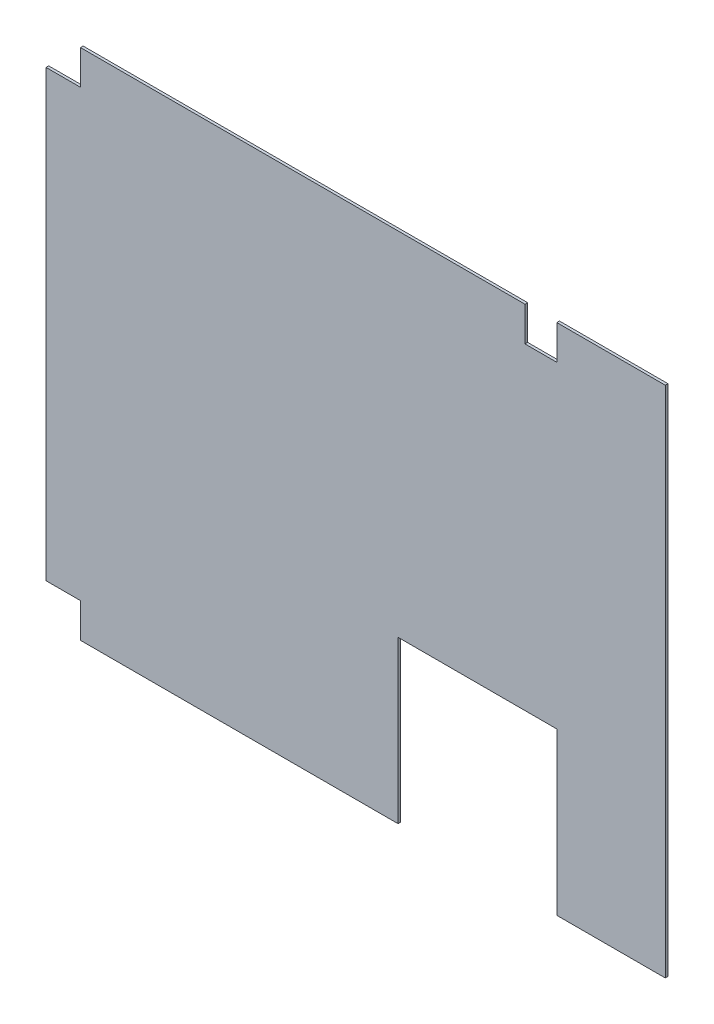
SolidWorks part; units mm, degrees
ref_plane "Front Plane" through (0, 0, 0) normal (0, 0, 1) x (1, 0, 0)
ref_plane "Top Plane" through (0, 0, 0) normal (0, 1, 0) x (1, 0, 0)
ref_plane "Right Plane" through (0, 0, 0) normal (1, 0, 0) x (0, 0, -1)
sketch "Sketch1" plane through (0, 0, 0) normal (0, 0, 1) x (1, 0, 0)
  line L1 (-371.475, -307.975) -> (371.475, -307.975)
  line L2 (-371.475, -307.975) -> (-371.475, 307.975)
  line L3 (-371.475, 307.975) -> (371.475, 307.975)
  line L4 (371.475, -307.975) -> (371.475, 307.975)
  line L5 (-371.475, -307.975) -> (371.475, 307.975) construction
  line L6 (-371.475, 307.975) -> (371.475, -307.975) construction
  point P0 (0, 0)
  dimension "D1" = 742.95
  dimension "D2" = 615.95
extrude "Boss-Extrude1" add sketch "Sketch1" along normal blind 3.175
sketch "Sketch2" plane through (0, 0, 3.175) normal (0, 0, 1) x (1, 0, 0)
  line L0 (371.475, 307.975) -> (-371.475, 307.975) construction
  line L1 (-371.475, 307.975) -> (-330.2, 307.975)
  line L2 (-371.475, 307.975) -> (-371.475, 266.7)
  line L3 (-371.475, 266.7) -> (-330.2, 266.7)
  line L4 (-330.2, 307.975) -> (-330.2, 266.7)
  line L5 (-371.475, 307.975) -> (-371.475, -307.975) construction
  line L6 (371.475, -307.975) -> (371.475, 307.975) construction
  line L7 (-371.475, -307.975) -> (-330.2, -307.975)
  line L8 (-371.475, -307.975) -> (-371.475, -266.7)
  line L9 (-371.475, -266.7) -> (-330.2, -266.7)
  line L10 (-330.2, -307.975) -> (-330.2, -266.7)
  line L11 (203.2, 307.975) -> (241.3, 307.975)
  line L12 (203.2, 307.975) -> (203.2, 266.7)
  line L13 (203.2, 266.7) -> (241.3, 266.7)
  line L14 (241.3, 307.975) -> (241.3, 266.7)
  line L15 (-371.475, -307.975) -> (371.475, -307.975) construction
  line L16 (50.8, -307.975) -> (241.3, -307.975)
  line L17 (50.8, -307.975) -> (50.8, -114.3)
  line L18 (50.8, -114.3) -> (241.3, -114.3)
  line L19 (241.3, -307.975) -> (241.3, -114.3)
  point P26 (203.2, -218.8248)
  point P27 (33.3442, -106.0231)
  dimension "D1" = 41.275
  dimension "D2" = 41.275
  dimension "D3" = 130.175
  dimension "D4" = 38.1
  dimension "D5" = 152.4
  dimension "D6" = 152.4
extrude "Cut-Extrude1" cut sketch "Sketch2" against normal through all
